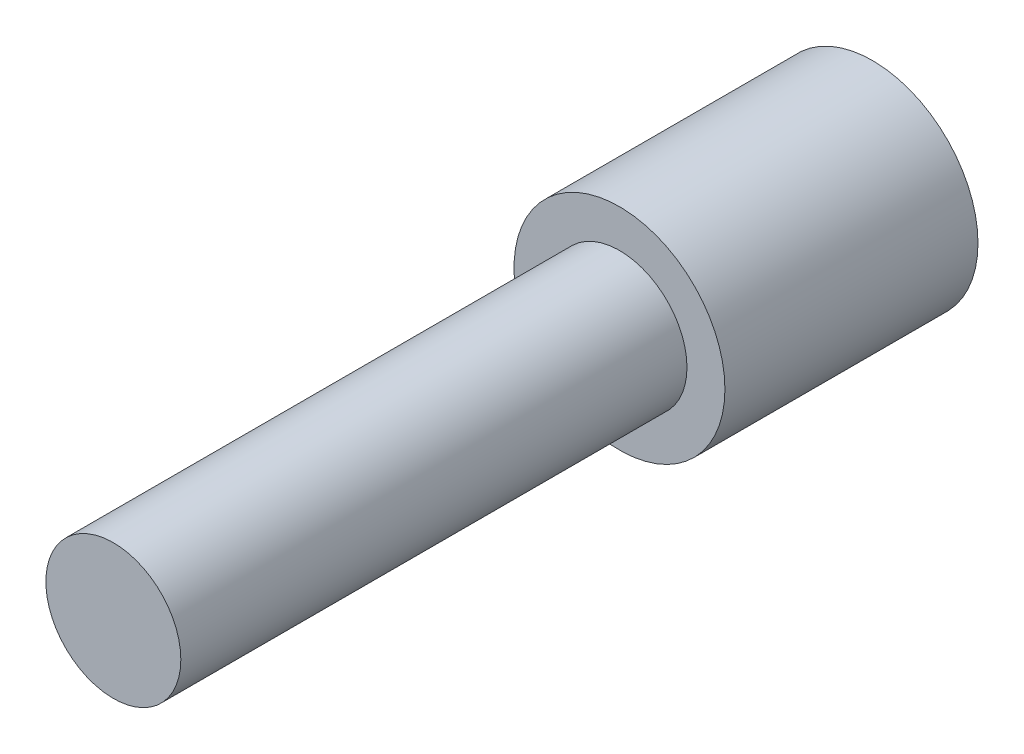
SolidWorks part; units mm, degrees
ref_plane "Front Plane" through (0, 0, 0) normal (0, 0, 1) x (1, 0, 0)
ref_plane "Top Plane" through (0, 0, 0) normal (0, 1, 0) x (1, 0, 0)
ref_plane "Right Plane" through (0, 0, 0) normal (1, 0, 0) x (0, 0, -1)
sketch "Sketch1" plane through (0, 0, 0) normal (0, 0, 1) x (1, 0, 0)
  circle A0 centre (0, 0) radius 6.25
  circle A1 centre (0, 0) radius 4
  dimension "D1" = 12.5
  dimension "D2" = 8
extrude "Boss-Extrude1" add sketch "Sketch1" along normal blind 15 contours A1 | A0 A1 region at (-6.0732, 0, 0) region at (0, 0, 0)
extrude "Boss-Extrude2" add sketch "Sketch1<3>" along normal blind 30 from surface contours A1 starting at face at (6.25, 0, 15)
sketch "Sketch1<3>" plane through (0, 0, 0) normal (0, 0, 1) x (1, 0, 0) same geometry as "Sketch1"
sketch "Sketch2" plane through (0, 0, 0) normal (0, 0, -1) x (-1, 0, 0)
  circle A0 centre (0, 0) radius 2
  dimension "D1" = 4
extrude "Cut-Extrude1" cut sketch "Sketch2" against normal blind 12
